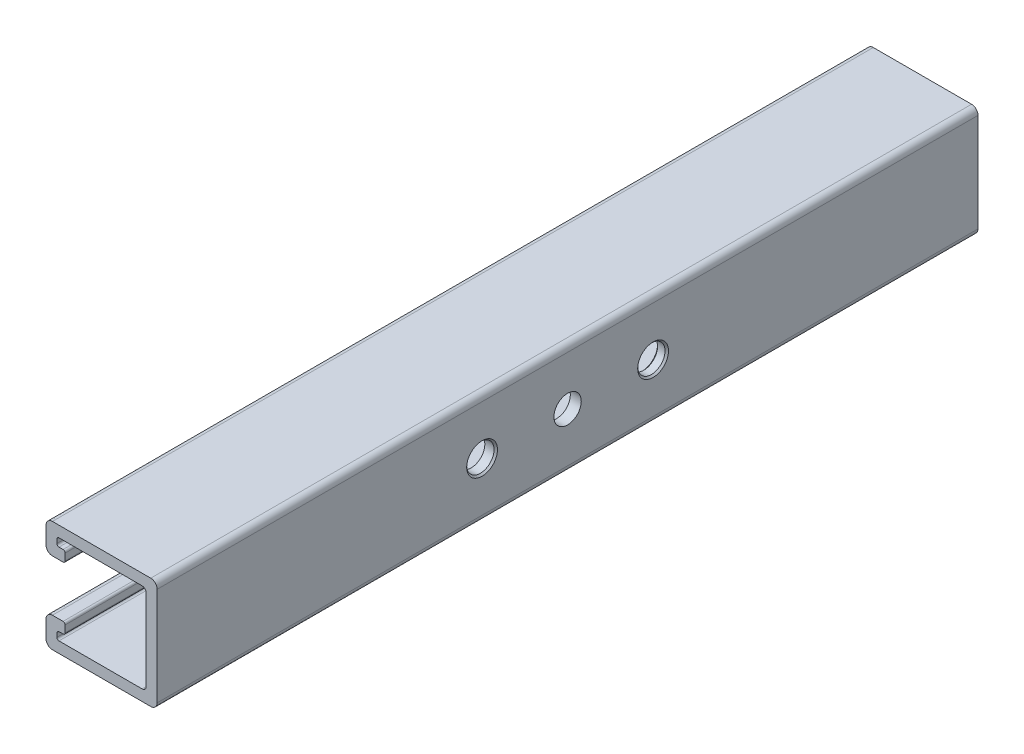
SolidWorks part; units mm, degrees
material "S-Glass Fiber"
ref_plane "Front Plane" through (0, 0, 0) normal (0, 0, 1) x (1, 0, 0)
ref_plane "Top Plane" through (0, 0, 0) normal (0, 1, 0) x (1, 0, 0)
ref_plane "Right Plane" through (0, 0, 0) normal (1, 0, 0) x (0, 0, -1)
sketch "Sketch1" plane through (0, 0, 0) normal (0, 0, 1) x (1, 0, 0)
  line L0 (-13.5255, 9.525) -> (-18.2499, 9.525)
  line L1 (-20.6375, 11.9126) -> (-20.6375, 18.2499)
  line L2 (-18.2499, 20.6375) -> (18.2499, 20.6375)
  line L3 (20.6375, 18.2499) -> (20.6375, -18.2499)
  line L4 (18.2499, -20.6375) -> (-18.2499, -20.6375)
  line L5 (-20.6375, -18.2499) -> (-20.6375, -11.9126)
  line L6 (-18.2499, -9.525) -> (-13.5255, -9.525)
  line L7 (0, 0) -> (20.6375, 0) construction
  line L8 (0, 0) -> (0, 20.6375) construction
  arc A0 (-20.6375, 18.2499) -> (-18.2499, 20.6375) centre (-18.2499, 18.2499) cw
  arc A1 (-18.2499, 9.525) -> (-20.6375, 11.9126) centre (-18.2499, 11.9126) cw
  arc A2 (-20.6375, -11.9126) -> (-18.2499, -9.525) centre (-18.2499, -11.9126) cw
  arc A3 (-18.2499, -20.6375) -> (-20.6375, -18.2499) centre (-18.2499, -18.2499) cw
  arc A4 (20.6375, -18.2499) -> (18.2499, -20.6375) centre (18.2499, -18.2499) cw
  arc A5 (18.2499, 20.6375) -> (20.6375, 18.2499) centre (18.2499, 18.2499) cw
  point P14 (-20.6375, 20.6375)
  point P23 (20.6375, -20.6375)
  point P26 (20.6375, 20.6375)
  dimension "D4" = 2.3876
  dimension "D1" = 41.275
  dimension "D2" = 41.275
  dimension "D3" = 19.05
  dimension "D5" = 7.112
extrude "Extrude-Thin1" add sketch "Sketch1" against normal blind 304.8 thin thin type one direction wall 4.064
fillet "Fillet2" radius 0.762 8 edges at (-16.5735, 13.589, -152.4) (-16.5735, -16.5735, -152.4) (-16.5735, 16.5735, -152.4) (-13.5255, 13.589, -152.4) (-13.5255, 9.525, -152.4) (-13.5255, -9.525, -152.4) (-13.5255, -13.589, -152.4) (-16.5735, -13.589, -152.4)
fillet "Fillet3" radius 1.524 2 edges at (16.5735, 16.5735, -152.4) (16.5735, -16.5735, -152.4)
sketch "Sketch3" plane through (0, 0, 0) normal (1, 0, 0) x (0, 0, -1)
  line L0 (0, 0) -> (304.8, 0) construction
  line L1 (304.8, 18.2499) -> (304.8, -18.2499) construction
  line L2 (0, 0) -> (0, 20.6375) construction
  line L3 (304.8, 0) -> (304.8, 20.6375) construction
  line L4 (304.8, 20.6375) -> (0, 20.6375) construction
  point P3 (101.6, 0)
  point P4 (203.2, 0)
  dimension "D1" = 101.6
  dimension "D2" = 101.6
sketch "Sketch4" plane through (20.6375, 0, 0) normal (1, 0, 0) x (0, 0, -1)
  line L0 (0, 0) -> (304.8, 0) construction
  line L1 (0, 18.2499) -> (0, -18.2499) construction
  line L2 (304.8, 18.2499) -> (304.8, -18.2499) construction
  line L3 (184.15, 5.08) -> (152.4, 5.08) construction
  line L4 (152.4, 5.08) -> (120.65, 5.08) construction
  circle A0 centre (152.4, 0) radius 5.08
  circle A1 centre (184.15, 0) radius 5.08
  circle A2 centre (120.65, 0) radius 5.08
  dimension "D1" = 10.16
  dimension "D2" = 10.16
  dimension "D3" = 31.75
extrude "Cut-Extrude1" cut sketch "Sketch4" against normal through all
chamfer "Chamfer1" distance 0.635 angle 45 3 edges at (20.6375, 0, -125.73) (16.5735, 0, -179.07) (20.6375, 0, -189.23)
sketch "Sketch5" [suppressed] plane through (20.6375, 0, 0) normal (1, 0, 0) x (0, 0, -1)
  line L1 (304.8, -20.6375) -> (0, -20.6375) construction
  line L2 (304.8, -20.6375) -> (304.8, 20.6375)
  line L3 (304.8, 20.6375) -> (0, 20.6375) construction
  line L4 (0, -20.6375) -> (0, 20.6375)
  line L5 (304.8, -20.6375) -> (0, 20.6375) construction
  line L6 (304.8, 20.6375) -> (0, -20.6375) construction
  circle A0 centre (184.15, 0) radius 5.08 construction
  circle A1 centre (152.4, 0) radius 5.08 construction
  circle A2 centre (120.65, 0) radius 5.08 construction
  circle A3 centre (184.15, 0) radius 5.08
  circle A4 centre (152.4, 0) radius 5.08
  circle A5 centre (120.65, 0) radius 5.08
  point P0 (152.4, 0)
  point P7 (152.4, 0)
